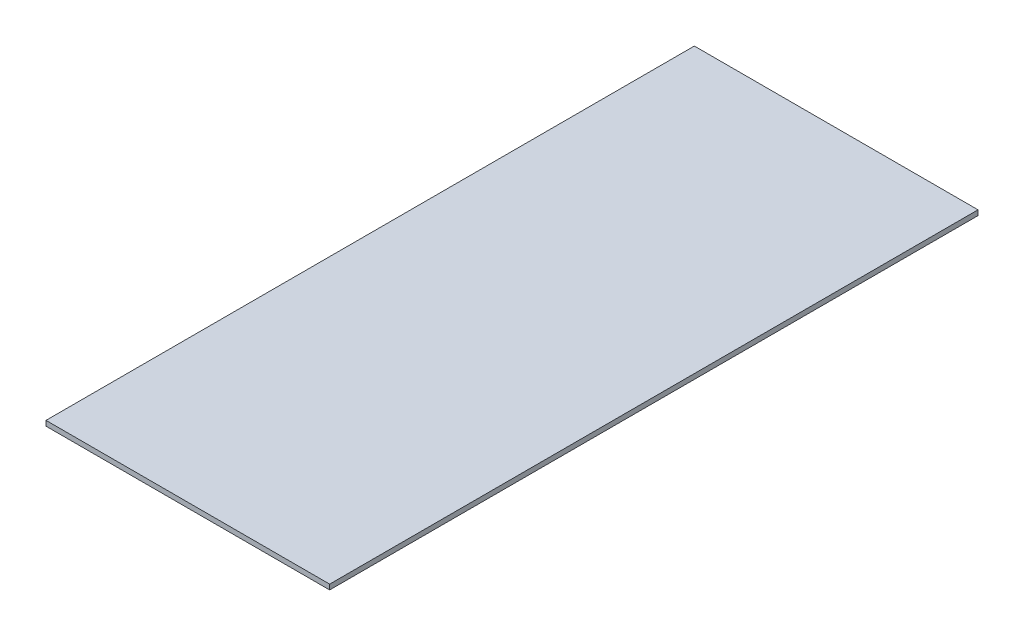
SolidWorks part; units mm, degrees
material "Acrylic (Medium-high impact)"
ref_plane "Front Plane" through (0, 0, 0) normal (0, 0, 1) x (1, 0, 0)
ref_plane "Top Plane" through (0, 0, 0) normal (0, 1, 0) x (1, 0, 0)
ref_plane "Right Plane" through (0, 0, 0) normal (1, 0, 0) x (0, 0, -1)
sketch "Sketch1" plane through (0, 0, 0) normal (0, 1, 0) x (1, 0, 0)
  line L0 (0, -223.52) -> (0, 223.52) construction
  line L1 (-88.9, -203.2) -> (88.9, -203.2)
  line L2 (-88.9, -203.2) -> (-88.9, 203.2)
  line L3 (-88.9, 203.2) -> (88.9, 203.2)
  line L4 (88.9, -203.2) -> (88.9, 203.2)
  line L5 (-88.9, -203.2) -> (88.9, 203.2) construction
  line L6 (-88.9, 203.2) -> (88.9, -203.2) construction
  point P0 (0, 0)
  dimension "D1" = 177.8
  dimension "D2" = 406.4
extrude "Boss-Extrude1" add sketch "Sketch1" along normal blind 3.175
sketch "Sketch2" [suppressed] plane through (0, 0, 0) normal (0, 1, 0) x (1, 0, 0)
  line L1 (-163.5125, -61.9125) -> (87.3125, -61.9125)
  line L2 (-163.5125, -61.9125) -> (-163.5125, -120.6136)
  line L3 (-163.5125, -120.6136) -> (87.3125, -120.6136)
  line L4 (87.3125, -61.9125) -> (87.3125, -120.6136)
  line L5 (163.5125, -61.9125) -> (163.5125, 61.9125) construction
  dimension "D1" = 76.2
  dimension "D2" = 58.7011
extrude "Boss-Extrude2" [suppressed] add sketch "Sketch2" along normal blind 3.175 contours L2 L3 L4 L1
